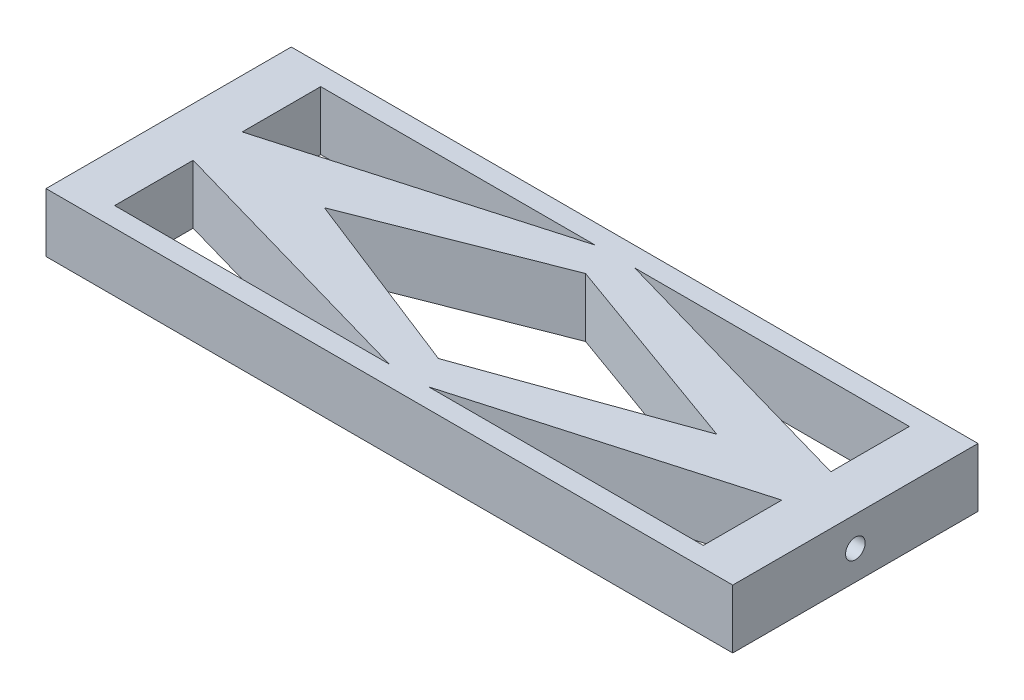
SolidWorks part; units mm, degrees
material "PLA"
ref_plane "Front" through (0, 0, 0) normal (0, 0, 1) x (1, 0, 0)
ref_plane "Top" through (0, 0, 0) normal (0, 1, 0) x (1, 0, 0)
ref_plane "Right" through (0, 0, 0) normal (1, 0, 0) x (0, 0, -1)
sketch "Sketch1" plane through (0, 0, 0) normal (0, 1, 0) x (1, 0, 0)
  line L1 (44.45, -15.875) -> (-44.45, -15.875)
  line L2 (44.45, -15.875) -> (44.45, 15.875)
  line L3 (44.45, 15.875) -> (-44.45, 15.875)
  line L4 (-44.45, -15.875) -> (-44.45, 15.875)
  line L5 (44.45, -15.875) -> (-44.45, 15.875) construction
  line L6 (44.45, 15.875) -> (-44.45, -15.875) construction
  point P0 (0, 0)
  dimension "D1" = 31.75
  dimension "D2" = 88.9
extrude "Boss-Extrude1" add sketch "Sketch1" along normal blind 7.62
sketch "Sketch2" plane through (0, 7.62, 0) normal (0, 1, 0) x (1, 0, 0)
  line L0 (-38.1, 3.175) -> (-38.1, 13.335)
  line L1 (-38.1, 13.335) -> (-2.564, 13.335)
  line L2 (-2.564, 13.335) -> (-38.1, 3.175)
  line L3 (44.45, 15.875) -> (-44.45, 15.875) construction
  line L4 (-44.45, 15.875) -> (-44.45, -15.875) construction
  line L5 (-38.1, -3.175) -> (-38.1, -13.335)
  line L6 (-38.1, -13.335) -> (-2.564, -13.335)
  line L7 (-2.564, -13.335) -> (-38.1, -3.175)
  line L8 (-44.45, -15.875) -> (44.45, -15.875) construction
  line L9 (2.54, 13.335) -> (38.1, 13.335)
  line L10 (38.1, 13.335) -> (38.1, 3.175)
  line L11 (38.1, 3.175) -> (2.54, 13.335)
  line L12 (44.45, -15.875) -> (44.45, 15.875) construction
  line L13 (38.1, -3.175) -> (38.1, -13.335)
  line L14 (38.1, -13.335) -> (2.54, -13.335)
  line L15 (2.54, -13.335) -> (38.1, -3.175)
  dimension "D1" = 10.16
  dimension "D2" = 2.54
  dimension "D3" = 6.35
  dimension "D4" = 35.536
  dimension "D5" = 35.536
  dimension "D6" = 2.54
  dimension "D7" = 10.16
  dimension "D8" = 35.56
  dimension "D9" = 6.35
  dimension "D10" = 10.16
  dimension "D11" = 35.56
  dimension "D12" = 10.16
extrude "Cut-Extrude1" cut sketch "Sketch2" against normal blind 29.464
sketch "Sketch3" plane through (0, 7.62, 0) normal (0, 1, 0) x (1, 0, 0)
  line L0 (0, 9.525) -> (-24.2924, 0)
  line L1 (0, -4.191) -> (0, 4.191) construction
  line L2 (-4.191, 0) -> (4.191, 0) construction
  line L3 (-24.2924, 0) -> (0, -9.525)
  line L4 (0, -9.525) -> (26.5076, 0)
  line L5 (26.5076, 0) -> (0, 9.525)
  line L6 (-44.45, -15.875) -> (44.45, -15.875) construction
  point P10 (0, 0)
  dimension "D1" = 50.8
  dimension "D2" = 19.05
  dimension "D3" = 6.35
extrude "Cut-Extrude2" cut sketch "Sketch3" against normal blind 29.464
sketch "Sketch4" plane through (44.45, 0, 0) normal (1, 0, 0) x (0, 0, -1)
  line L0 (0, 4.191) -> (0, -4.191) construction
  line L1 (17.4625, 0) -> (-17.4625, 0) construction
  circle A0 centre (0, 3.7869) radius 1.27
  dimension "D1" = 2.54
  dimension "D2" = 3.7869
extrude "Cut-Extrude3" cut sketch "Sketch4" against normal blind 7.62
sketch "Sketch5" plane through (-44.45, 0, 0) normal (-1, 0, 0) x (0, 0, 1)
  line L0 (0, -4.191) -> (0, 4.191) construction
  line L1 (17.4625, 0) -> (-17.4625, 0) construction
  circle A0 centre (0, 3.81) radius 1.27
  dimension "D1" = 2.54
  dimension "D2" = 3.81
extrude "Cut-Extrude4" cut sketch "Sketch5" against normal blind 7.62
